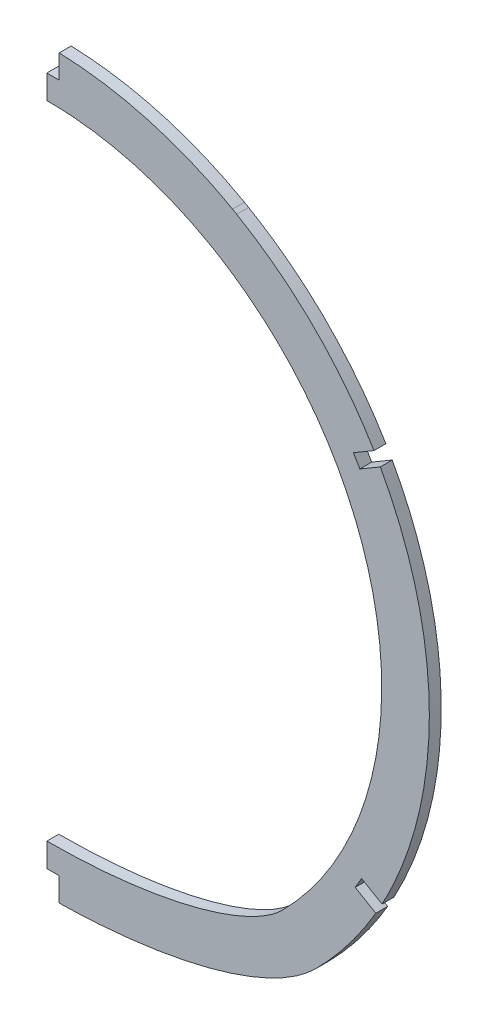
SolidWorks part; units mm, degrees
material "Balsa"
ref_plane "Front Plane" through (0, 0, 0) normal (0, 0, 1) x (1, 0, 0)
ref_plane "Top Plane" through (0, 0, 0) normal (0, 1, 0) x (1, 0, 0)
ref_plane "Right Plane" through (0, 0, 0) normal (1, 0, 0) x (0, 0, -1)
sketch "Sketch2" plane through (0, 0, 0) normal (0, 0, 1) x (1, 0, 0)
  spline S0 degree 3 poles (2568.0953, -4090.4659) (-4057.024, 3451.1389) (4945.1528, -1980.2124) (-4825.8731, 402.3844) knots -545.10296 -545.10296 -545.10296 -545.10296 547.49362 547.49362 547.49362 547.49362 only from (49.5009, 91.348) to (50.6103, 90.7129)
  spline S1 degree 3 poles (3341.4723, -3725.6669) (-100.6677, -22.1088) (-50.1916, -95.8099) (-74.4696, -70.0026) (-75.8372, -68.488) (-77.1861, -66.9319) (-78.5157, -65.3347) (-79.8244, -63.6962) (-81.5476, -61.4464) (-83.6416, -58.5297) (-85.6296, -55.5014) (-87.1622, -52.9973) (-88.2859, -51.0701) (-90.1147, -47.7724) (-92.5499, -42.8914) (-95.3516, -36.1752) (-97.8068, -28.8548) (-99.4166, -22.4927) (-100.4844, -16.9735) (-101.2174, -12.1158) (-101.8059, -6.1085) (-102.0556, 1.0556) (-101.6376, 11.9166) (-99.5817, 24.7034) (-94.9478, 39.4776) (-88.6565, 52.7081) (-80.0434, 65.5541) (-69.8712, 76.7554) (-58.637, 85.9148) (-47.202, 92.899) (-35.7905, 98.0522) (-24.0008, 101.7167) (-12.0295, 103.8942) (-3.6569, 104.3953) (0.9911, 104.3723) (2.6447, 104.3478) (5.2959, 104.2559) (8.9441, 104.0024) (12.9235, 103.5662) (16.8979, 102.9692) (20.8607, 102.2106) (24.805, 101.2899) (28.7242, 100.207) (32.6113, 98.9619) (36.4593, 97.5551) (39.9429, 96.1186) (42.4433, 94.9816) (43.9946, 94.2376) (44.9225, 93.7809) (45.8466, 93.3143) (46.7667, 92.8378) (47.6827, 92.3514) (70.4007, 80.003) (151.5153, 23.3747) (-4363.3748, 2440.7113) knots -0.313173 -0.313173 -0.313173 -0.313173 0.006795 0.013654 0.020575 0.02756 0.034609 0.041722 0.048899 0.063446 0.078252 0.085753 0.09332 0.100952 0.124124 0.148785 0.174948 0.202627 0.215494 0.232144 0.2526 0.276886 0.305032 0.363116 0.408011 0.462235 0.511576 0.564908 0.615598 0.658549 0.700916 0.742691 0.78387 0.82445 0.827809 0.831171 0.841279 0.854802 0.868378 0.882008 0.895692 0.909428 0.923217 0.93706 0.950955 0.964902 0.975398 0.978902 0.982411 0.985922 0.989437 0.992954 0.996476 1.262403 1.262403 1.262403 1.262403 only from (-71.6774, -72.9104) to (49.5009, 91.348)
  spline S2 degree 3 poles (-71.6774, -72.9104) (-72.1092, -72.4767) (-72.9729, -71.5936) (-74.4696, -70.0026) (-75.8372, -68.488) (-77.1861, -66.9319) (-78.5157, -65.3347) (-79.8244, -63.6962) (-81.5476, -61.4464) (-83.6416, -58.5297) (-85.6296, -55.5014) (-87.1622, -52.9973) (-88.2859, -51.0701) (-90.1147, -47.7724) (-92.5499, -42.8914) (-95.3516, -36.1752) (-97.8068, -28.8548) (-99.4166, -22.4927) (-100.4844, -16.9735) (-101.2174, -12.1158) (-101.8059, -6.1085) (-102.0556, 1.0556) (-101.6376, 11.9166) (-99.5817, 24.7034) (-94.9478, 39.4776) (-88.6565, 52.7081) (-80.0434, 65.5541) (-69.8712, 76.7554) (-58.637, 85.9148) (-47.202, 92.899) (-35.7905, 98.0522) (-24.0008, 101.7167) (-12.0295, 103.8942) (-3.6569, 104.3953) (0.9911, 104.3723) (2.6447, 104.3478) (5.2959, 104.2559) (8.9441, 104.0024) (12.9235, 103.5662) (16.8979, 102.9692) (20.8607, 102.2106) (24.805, 101.2899) (28.7242, 100.207) (32.6113, 98.9619) (36.4593, 97.5551) (39.9429, 96.1186) (42.4433, 94.9816) (43.9946, 94.2376) (44.9225, 93.7809) (45.8466, 93.3143) (46.7667, 92.8378) (47.6827, 92.3514) (48.5618, 91.8735) (49.1883, 91.5244) (49.5009, 91.348) knots 0 0 0 0 0.006795 0.013654 0.020575 0.02756 0.034609 0.041722 0.048899 0.063446 0.078252 0.085753 0.09332 0.100952 0.124124 0.148785 0.174948 0.202627 0.215494 0.232144 0.2526 0.276886 0.305032 0.363116 0.408011 0.462235 0.511576 0.564908 0.615598 0.658549 0.700916 0.742691 0.78387 0.82445 0.827809 0.831171 0.841279 0.854802 0.868378 0.882008 0.895692 0.909428 0.923217 0.93706 0.950955 0.964902 0.975398 0.978902 0.982411 0.985922 0.989437 0.992954 0.996476 1 1 1 1
  spline S3 degree 3 poles (49.5009, 91.348) (49.872, 91.1385) (50.2418, 90.9268) (50.6103, 90.7129) knots 0 0 0 0 1 1 1 1
  spline S4 degree 3 poles (-4193.7763, 2732.8048) (81.5381, 53.7028) (23.1515, 107.7521) (53.9325, 88.7036) (55.5798, 87.6387) (57.2181, 86.5331) (58.847, 85.3874) (60.4652, 84.2011) (62.6149, 82.559) (65.2687, 80.4032) (68.3802, 77.661) (71.4204, 74.7537) (74.3792, 71.6812) (77.2464, 68.4441) (79.5428, 65.6199) (81.3243, 63.2803) (82.6352, 61.4798) (83.9151, 59.6395) (85.6826, 56.9767) (87.8969, 53.3695) (90.4626, 48.6769) (92.8892, 43.6261) (95.1327, 38.2157) (97.1465, 32.4482) (98.8821, 26.3306) (100.2892, 19.8751) (101.2586, 13.4739) (101.8173, 7.2467) (102.0152, 1.305) (101.8786, -4.6242) (101.3926, -10.7347) (100.5371, -16.8676) (99.3294, -22.8638) (97.8936, -28.3722) (96.657, -32.2698) (95.7856, -34.7444) (95.046, -36.7643) (93.9532, -39.5358) (92.4358, -43.007) (90.8217, -46.3649) (89.1186, -49.6082) (87.3342, -52.7363) (85.4757, -55.7486) (83.5505, -58.6453) (81.5655, -61.4266) (79.3077, -64.3807) (77.437, -66.6472) (76.0073, -68.2889) (75.2951, -69.0897) (74.579, -69.8782) (73.8594, -70.6545) (73.1363, -71.4184) (59.0939, -85.9325) (120.7935, -16.6257) (-3396.6628, -3673.2191) knots -0.504739 -0.504739 -0.504739 -0.504739 0.010157 0.020393 0.030709 0.041103 0.051576 0.062128 0.072758 0.094254 0.116062 0.138181 0.16061 0.183347 0.206391 0.218027 0.22974 0.241529 0.253393 0.280162 0.30828 0.337739 0.36853 0.400644 0.434071 0.4688 0.504821 0.536145 0.567394 0.59857 0.62967 0.664059 0.696204 0.726123 0.75383 0.760691 0.767516 0.787768 0.807688 0.827278 0.84654 0.865477 0.884089 0.902378 0.920346 0.937994 0.961032 0.966703 0.97234 0.977942 0.983508 0.98904 0.994538 1.266327 1.266327 1.266327 1.266327 only from (50.6103, 90.7129) to (71.6784, -72.9104)
  spline S5 degree 3 poles (50.6103, 90.7129) (51.1284, 90.4118) (52.1672, 89.796) (53.9325, 88.7036) (55.5798, 87.6387) (57.2181, 86.5331) (58.847, 85.3874) (60.4652, 84.2011) (62.6149, 82.559) (65.2687, 80.4032) (68.3802, 77.661) (71.4204, 74.7537) (74.3792, 71.6812) (77.2464, 68.4441) (79.5428, 65.6199) (81.3243, 63.2803) (82.6352, 61.4798) (83.9151, 59.6395) (85.6826, 56.9767) (87.8969, 53.3695) (90.4626, 48.6769) (92.8892, 43.6261) (95.1327, 38.2157) (97.1465, 32.4482) (98.8821, 26.3306) (100.2892, 19.8751) (101.2586, 13.4739) (101.8173, 7.2467) (102.0152, 1.305) (101.8786, -4.6242) (101.3926, -10.7347) (100.5371, -16.8676) (99.3294, -22.8638) (97.8936, -28.3722) (96.657, -32.2698) (95.7856, -34.7444) (95.046, -36.7643) (93.9532, -39.5358) (92.4358, -43.007) (90.8217, -46.3649) (89.1186, -49.6082) (87.3342, -52.7363) (85.4757, -55.7486) (83.5505, -58.6453) (81.5655, -61.4266) (79.3077, -64.3807) (77.437, -66.6472) (76.0073, -68.2889) (75.2951, -69.0897) (74.579, -69.8782) (73.8594, -70.6545) (73.1363, -71.4184) (72.3175, -72.2647) (71.8912, -72.6967) (71.6784, -72.9104) knots 0 0 0 0 0.010157 0.020393 0.030709 0.041103 0.051576 0.062128 0.072758 0.094254 0.116062 0.138181 0.16061 0.183347 0.206391 0.218027 0.22974 0.241529 0.253393 0.280162 0.30828 0.337739 0.36853 0.400644 0.434071 0.4688 0.504821 0.536145 0.567394 0.59857 0.62967 0.664059 0.696204 0.726123 0.75383 0.760691 0.767516 0.787768 0.807688 0.827278 0.84654 0.865477 0.884089 0.902378 0.920346 0.937994 0.961032 0.966703 0.97234 0.977942 0.983508 0.98904 0.994538 1 1 1 1
  spline S6 degree 3 poles (-4835.9061, 806.008) (5645.7753, -391.3089) (-5645.7177, -391.3145) (4835.7602, 805.9912) knots -2.930767 -2.930767 -2.930767 -2.930767 3.930735 3.930735 3.930735 3.930735 weights 1 1 1 1 only from (71.6784, -72.9104) to (-71.6774, -72.9104)
  spline S7 degree 3 poles (71.6784, -72.9104) (46.3599, -98.3417) (-46.3589, -98.3417) (-71.6774, -72.9104) knots 0 0 0 0 1 1 1 1 weights 1 1 1 1
  spline S8 degree 1 poles (-62.6772, -63.9502) (43.2582, 80.2883) knots 0 0 1 1 construction
  spline S9 degree 1 poles (43.2582, 80.2883) (44.2327, 79.7303) knots 0 0 1 1 construction
  spline S10 degree 1 poles (44.2327, 79.7303) (62.6782, -63.9502) knots 0 0 1 1 construction
  spline S11 degree 1 poles (62.6782, -63.9502) (-62.6772, -63.9502) knots 0 0 1 1 construction
  spline S12 degree 3 poles (-62.6772, -63.9502) (-62.8955, -63.7309) (-63.3217, -63.2983) (-64.0021, -62.5921) (-64.7538, -61.7946) (-65.7039, -60.7646) (-66.8046, -59.5274) (-68.5568, -57.4681) (-70.6482, -54.8355) (-73.8114, -50.469) (-77.3945, -44.7561) (-82.3029, -35.1354) (-86.8108, -22.36) (-90.3543, -0.9674) (-87.6499, 26.3501) (-73.3334, 55.9721) (-49.624, 78.7088) (-24.4872, 89.3835) (-3.091, 92.1159) (13.039, 91.1975) (26.1203, 87.9966) (34.8794, 84.5248) (39.1021, 82.5104) (41.2143, 81.4108) (42.347, 80.7976) (42.9592, 80.4569) (43.2582, 80.2883) knots 0 0 0 0 0.003906 0.007812 0.011719 0.015625 0.023437 0.03125 0.046875 0.062499 0.093749 0.124999 0.187498 0.249998 0.374997 0.499996 0.624995 0.749994 0.812493 0.874993 0.937492 0.968742 0.984367 0.992179 0.996085 0.999992 0.999992 0.999992 0.999992
  spline S13 degree 3 poles (43.2582, 80.2883) (43.3397, 80.2423) (43.5025, 80.15) (43.7464, 80.0108) (43.9898, 79.871) (44.1518, 79.7773) (44.2327, 79.7303) knots 0.002022 0.002022 0.002022 0.002022 0.251014 0.500005 0.748996 0.997987 0.997987 0.997987 0.997987
  spline S14 degree 3 poles (44.2327, 79.7303) (44.5844, 79.526) (45.2596, 79.1276) (46.4154, 78.4223) (47.5738, 77.6928) (49.0079, 76.7584) (50.8048, 75.5306) (53.6072, 73.4932) (57.0034, 70.7903) (64.7641, 63.8421) (74.8536, 51.7693) (84.3118, 33.0007) (89.3026, 12.5818) (89.5941, -8.4639) (85.1673, -29.0225) (78.4712, -43.2887) (72.7378, -52.0045) (70.1455, -55.4923) (67.9548, -58.1887) (66.5372, -59.8344) (65.3768, -61.1241) (64.6361, -61.9238) (64.0489, -62.544) (63.5408, -63.0721) (63.0657, -63.5594) (62.8132, -63.8146) (62.6782, -63.9502) knots 0.000015 0.000015 0.000015 0.000015 0.007827 0.015639 0.023452 0.031264 0.046889 0.062514 0.093763 0.125013 0.250011 0.375009 0.500007 0.625005 0.750004 0.875002 0.906251 0.937501 0.953126 0.96875 0.976563 0.984375 0.988281 0.992188 0.996094 1 1 1 1
  spline S15 degree 3 poles (62.6782, -63.9502) (62.4421, -64.1873) (61.9735, -64.6322) (60.8483, -65.5949) (59.1789, -66.8259) (56.7375, -68.3252) (52.9423, -70.2888) (47.261, -72.5995) (39.2215, -74.978) (30.229, -76.8801) (17.3048, -78.7217) (0.0005, -79.6587) (-17.3038, -78.7217) (-30.228, -76.8801) (-39.2204, -74.978) (-47.2599, -72.5995) (-52.9413, -70.2888) (-56.7364, -68.3252) (-59.1779, -66.8259) (-60.8473, -65.5949) (-61.9724, -64.6322) (-62.4411, -64.1873) (-62.6772, -63.9502) knots 0 0 0 0 0.015625 0.03125 0.0625 0.09375 0.125 0.1875 0.25 0.3125 0.375 0.5 0.625 0.6875 0.75 0.8125 0.875 0.90625 0.9375 0.96875 0.984375 1 1 1 1
  dimension "D1" = 12.7
extrude "Boss-Extrude1" add sketch "Sketch2" against normal blind 3.175
sketch "Sketch3" plane through (0, 0, 0) normal (1, 0, 0) x (0, 0, -1)
  line L1 (-61.0107, 158.0584) -> (68.3789, 158.0584)
  line L2 (-61.0107, 158.0584) -> (-61.0107, -136.6623)
  line L3 (-61.0107, -136.6623) -> (68.3789, -136.6623)
  line L4 (68.3789, 158.0584) -> (68.3789, -136.6623)
extrude "Cut-Extrude1" cut sketch "Sketch3" against normal through all
sketch "Sketch4" plane through (0, 0, -3.175) normal (0, 0, -1) x (-1, 0, 0)
  line L0 (0, 0) -> (0, 91.6752) construction
  line L1 (0, 91.6752) -> (0, 98.0252) construction
  line L2 (-3.302, 98.0252) -> (3.302, 98.0252)
  line L3 (0, 98.0252) -> (0, 110.7252)
  line L4 (3.302, 98.0252) -> (3.302, 110.7252)
  line L5 (-3.302, 110.7252) -> (3.302, 110.7252)
  line L6 (77.1004, 46.575) -> (82.577, 49.789) construction
  line L7 (81.7221, 51.2458) -> (83.4319, 48.3323)
  line L8 (77.1004, 46.575) -> (0, 1.327) construction
  line L9 (81.7221, 51.2458) -> (92.6752, 57.6738)
  line L10 (83.4319, 48.3323) -> (94.385, 54.7603)
  line L11 (92.6752, 57.6738) -> (94.385, 54.7603)
  line L12 (77.572, -44.1978) -> (83.0486, -47.4118) construction
  line L13 (77.572, -44.1978) -> (0, 1.327) construction
  line L14 (82.1936, -48.8686) -> (83.9035, -45.955)
  line L15 (82.1936, -48.8686) -> (93.1467, -55.2966)
  line L16 (83.9035, -45.955) -> (94.8566, -52.3831)
  line L17 (93.1467, -55.2966) -> (94.8566, -52.3831)
  line L18 (0, 1.327) -> (0, -79.2839) construction
  line L19 (0, -79.2839) -> (0, -85.6339) construction
  line L20 (-3.302, -85.6339) -> (3.302, -85.6339)
  line L21 (0, -85.6339) -> (0, -98.3339)
  line L22 (3.302, -85.6339) -> (3.302, -98.3339)
  line L23 (-3.302, -98.3339) -> (3.302, -98.3339)
  line L24 (-77.572, -44.1978) -> (0, 1.327) construction
  line L25 (-77.572, -44.1978) -> (-83.0486, -47.4118) construction
  line L26 (-77.1004, 46.575) -> (0, 1.327) construction
  line L27 (-77.1004, 46.575) -> (-82.577, 49.789) construction
  line L28 (-3.302, -85.6339) -> (-3.302, -98.3339)
  line L29 (-93.1467, -55.2966) -> (-94.8566, -52.3831)
  line L30 (-83.9035, -45.955) -> (-94.8566, -52.3831)
  line L31 (-82.1936, -48.8686) -> (-93.1467, -55.2966)
  line L32 (-82.1936, -48.8686) -> (-83.9035, -45.955)
  line L33 (-92.6752, 57.6738) -> (-94.385, 54.7603)
  line L34 (-83.4319, 48.3323) -> (-94.385, 54.7603)
  line L35 (-81.7221, 51.2458) -> (-92.6752, 57.6738)
  line L36 (-81.7221, 51.2458) -> (-83.4319, 48.3323)
  line L37 (-3.302, 98.0252) -> (-3.302, 110.7252)
  point P15 (83.0486, -47.4118)
  point P25 (0, 0)
  line M6 (0, -91.9839) -> (0, -79.2839)
  line M11 (0, 91.6752) -> (0, 104.3756)
  dimension "D1" = 91.6752
  dimension "D2" = 6.35
  dimension "D3" = 3.302
  dimension "D4" = 12.7
  dimension "D5" = 59.593
  dimension "D6" = 1.327
  dimension "D7" = 89.3972
  dimension "D8" = 6.35
  dimension "D9" = 3.3782
  dimension "D10" = 12.7
  dimension "D11" = 59.593
  dimension "D12" = 89.944
  dimension "D13" = 6.35
  dimension "D14" = 3.3782
  dimension "D15" = 12.7
  dimension "D16" = 80.6109
  dimension "D17" = 6.35
  dimension "D18" = 3.302
  dimension "D19" = 12.7
extrude "Cut-Extrude2" cut sketch "Sketch4" against normal through all contours L37 L2 M11 | L36 L35 L34 | L31 L32 L30 | L20 L28 M6 region at (1.651, 104.3752, -3.175) region at (1.651, -91.9839, -3.175) region at (88.5251, -50.6258, -3.175) region at (88.0535, 53.003, -3.175)
